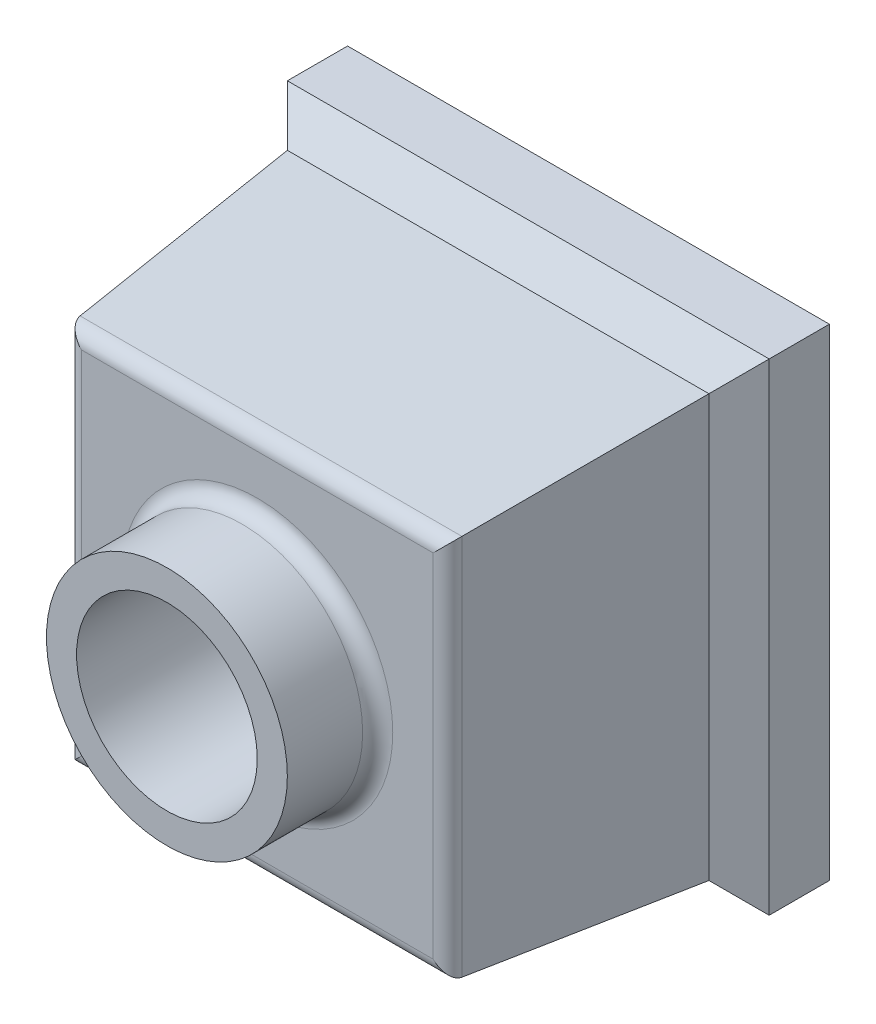
SolidWorks part; units mm, degrees
ref_plane "Front Plane" through (0, 0, 0) normal (0, 0, 1) x (1, 0, 0)
ref_plane "Top Plane" through (0, 0, 0) normal (0, 1, 0) x (1, 0, 0)
ref_plane "Right Plane" through (0, 0, 0) normal (1, 0, 0) x (0, 0, -1)
sketch "Sketch1" plane through (0, 0, 0) normal (0, 0, 1) x (1, 0, 0)
  line L1 (0, 0) -> (160, 0)
  line L2 (0, 0) -> (0, 160)
  line L3 (0, 160) -> (160, 160)
  line L4 (160, 0) -> (160, 160)
  dimension "D1" = 160
  dimension "D2" = 160
extrude "Boss-Extrude1" add sketch "Sketch1" along normal blind 30
sketch "Sketch2" plane through (0, 0, 30) normal (0, 0, 1) x (1, 0, 0)
  line L16 (10, 10) -> (150, 10)
  line L17 (150, 10) -> (150, 150)
  line L18 (10, 150) -> (10, 10)
  line L19 (150, 150) -> (10, 150)
  line L20 (10, 10) -> (150, 10)
  line L21 (150, 10) -> (150, 150)
  line L22 (10, 150) -> (10, 10)
  line L23 (150, 150) -> (10, 150)
  dimension "D1" = 10
extrude "Boss-Extrude2" add sketch "Sketch2" along normal blind 80 draft 5
sketch "Sketch3" plane through (0, 0, 110) normal (0, 0, 1) x (1, 0, 0)
  line L0 (16.9991, 16.9991) -> (143.0009, 143.0009) construction
  circle A0 centre (80, 80) radius 40
  dimension "D1" = 80
extrude "Boss-Extrude3" add sketch "Sketch3" along normal blind 30
sketch "Sketch4" plane through (0, 0, 140) normal (0, 0, 1) x (1, 0, 0)
  circle A0 centre (80, 80) radius 30
  dimension "D1" = 60
extrude "Cut-Extrude1" cut sketch "Sketch4" against normal through all both and the other way through all
fillet "Fillet1" radius 5 5 edges at (80, 143.0009, 110) (143.0009, 80, 110) (80, 16.9991, 110) (16.9991, 80, 110) (120, 80, 110)
chamfer "Chamfer1" distance 10 angle 45 4 edges at (0, 80, 30) (80, 0, 30) (160, 80, 30) (80, 160, 30)
